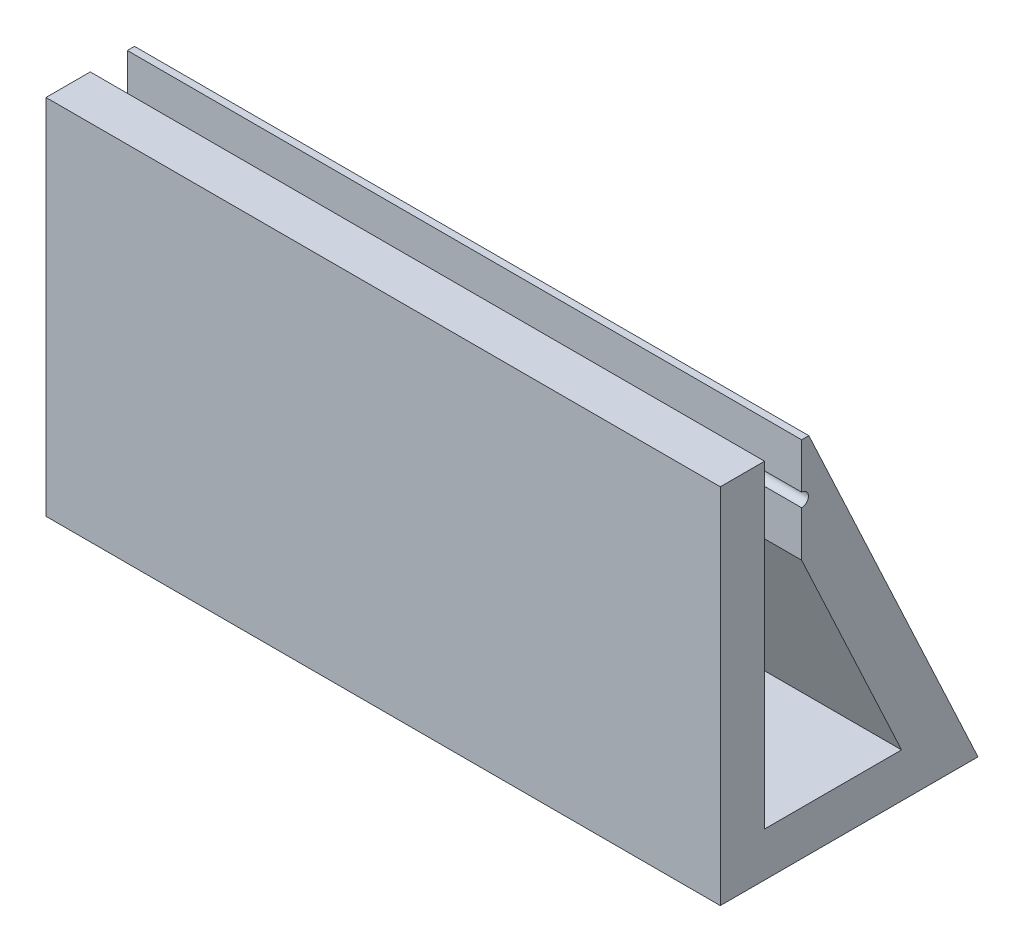
SolidWorks part; units mm, degrees
ref_plane "Front Plane" through (0, 0, 0) normal (0, 0, 1) x (1, 0, 0)
ref_plane "Top Plane" through (0, 0, 0) normal (0, 1, 0) x (1, 0, 0)
ref_plane "Right Plane" through (0, 0, 0) normal (1, 0, 0) x (0, 0, -1)
sketch "Sketch1" plane through (0, 0, 0) normal (1, 0, 0) x (0, 0, -1)
  line L0 (0, 0) -> (7.643, 0)
  line L1 (0, 6.0362) -> (1.3128, 6.0362) construction
  line L2 (2.4128, 10.7595) -> (2.4128, 7.6668) construction
  line L3 (2.4128, 7.6668) -> (5.3757, 1.3128)
  line L4 (5.3757, 1.3128) -> (1.3128, 1.3128)
  line L5 (1.3128, 1.3128) -> (1.3128, 10.7595)
  line L6 (1.3128, 10.7595) -> (0, 10.7595)
  line L7 (0, 10.7595) -> (0, 0)
  line L8 (2.4128, 10.7595) -> (2.4128, 9.4131)
  line L9 (2.4128, 9.0131) -> (2.4128, 7.6668)
  line L10 (2.4128, 10.7595) -> (2.6257, 10.7595)
  line L11 (2.6257, 10.7595) -> (7.643, 0)
  line L12 (3.3443, 1.3128) -> (3.3443, 0) construction
  arc A0 (2.4128, 9.4131) -> (2.4128, 9.0131) centre (2.4128, 9.2131) cw
  dimension "D1" = 0.2
  dimension "D2" = 1.1
  dimension "D3" = 65
  dimension "D4" = 1.5
extrude "Boss-Extrude1" add sketch "Sketch1" along normal mid plane 20 contours L8 A0 L9 L3 L4 L5 L6 L7 L0 L11 L10
